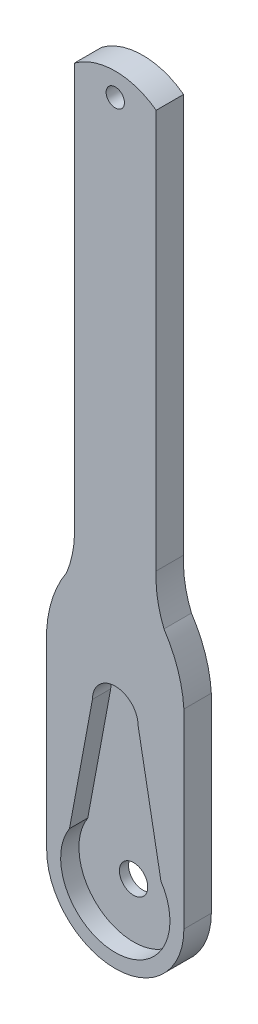
SolidWorks part; units mm, degrees
material "ABS"
ref_plane "Front Plane" through (0, 0, 0) normal (0, 0, 1) x (1, 0, 0)
ref_plane "Top Plane" through (0, 0, 0) normal (0, 1, 0) x (1, 0, 0)
ref_plane "Right Plane" through (0, 0, 0) normal (1, 0, 0) x (0, 0, -1)
sketch "Sketch1" plane through (0, 0, 0) normal (0, 0, 1) x (1, 0, 0)
  line L0 (5, 24.25) -> (2.4925, 10.7598)
  line L1 (0, 0) -> (15, 0)
  line L2 (0, 0) -> (0, 85)
  line L3 (0, 85) -> (15, 85)
  line L4 (15, 0) -> (15, 85)
  line L5 (7.5, 0) -> (15, 0)
  line L6 (15, 0) -> (15, 7.5)
  line L7 (7.5, 7.5) -> (7.5, 26.75) construction
  line L10 (10, 24.25) -> (12.4925, 10.7826)
  arc A0 (0, 7.5) -> (15, 7.5) centre (7.5, 7.5) ccw
  arc A2 (10, 24.25) -> (5, 24.25) centre (7.5, 24.25) ccw
  arc A3 (2.4925, 10.7598) -> (12.4925, 10.7826) centre (7.5, 7.5) ccw
  dimension "D3" = 10
  dimension "D4" = 5.975
  dimension "D6" = 5
  dimension "D1" = 15
  dimension "D2" = 85
  dimension "D5" = 19.25
extrude "Boss-Extrude1" add sketch "Sketch1" along normal blind 3 contours L2 A0 L4 L3 A2 region at (7.5003, 49.2811, 0)
extrude "Boss-Extrude2" add sketch "Sketch1<3>" along normal blind 1 contours A2 region at (7.4985, 12.5376, 0)
sketch "Sketch1<3>" plane through (0, 0, 0) normal (0, 0, 1) x (1, 0, 0) same geometry as "Sketch1"
sketch "Sketch2" plane through (0, 0, 3) normal (0, 0, 1) x (1, 0, 0)
  line L0 (0, 85) -> (15, 85) construction
  line L1 (15, 7.5) -> (15, 85) construction
  line L3 (0, 85) -> (7.5, 85)
  line L4 (7.5, 85) -> (8.366, 85)
  line L6 (0, 7.5) -> (0, 85) construction
  line L7 (7.5, 91.1947) -> (7.5, -46.3008) construction
  line L8 (3.0299, 39.8913) -> (3.0299, 83.5223)
  line L9 (11.9701, 39.8913) -> (11.9701, 83.5223)
  arc A0 (11.9701, 83.5223) -> (3.0299, 83.5223) centre (7.5, 77.5) ccw
  arc A2 (10, 24.25) -> (5, 24.25) centre (7.5, 24.25) ccw construction
  arc A3 (0, 26.75) -> (2.1738, 34.8326) centre (13.1666, 27.5424) cw
  arc A4 (2.1738, 34.8326) -> (3.0299, 39.8913) centre (-8.6706, 39.2695) ccw
  arc A5 (12.8262, 34.8326) -> (11.9701, 39.8913) centre (23.6706, 39.2695) cw
  arc A6 (15, 26.75) -> (12.8262, 34.8326) centre (1.8334, 27.5424) ccw
  circle A9 centre (7.5, 82.5) radius 1
  arc A10 (2.4925, 10.7598) -> (12.4925, 10.7826) centre (7.5, 7.5) ccw construction
  circle A11 centre (7.5, 7.5) radius 1.55
  point P8 (7.5, 26.75)
  line M7 (0, 85) -> (0, 7.5)
  line M9 (15, 7.5) -> (15, 85)
  line M10 (15, 85) -> (0, 85)
  dimension "D1" = 2
  dimension "D3" = 3.1
  dimension "D2" = 75
extrude "Cut-Extrude1" cut sketch "Sketch2" against normal through all contours A0 M10 M7 | A0 M9 M10 | A9 | A11 region at (13.4872, 59.5795, 3) region at (1.5128, 59.5795, 3)
